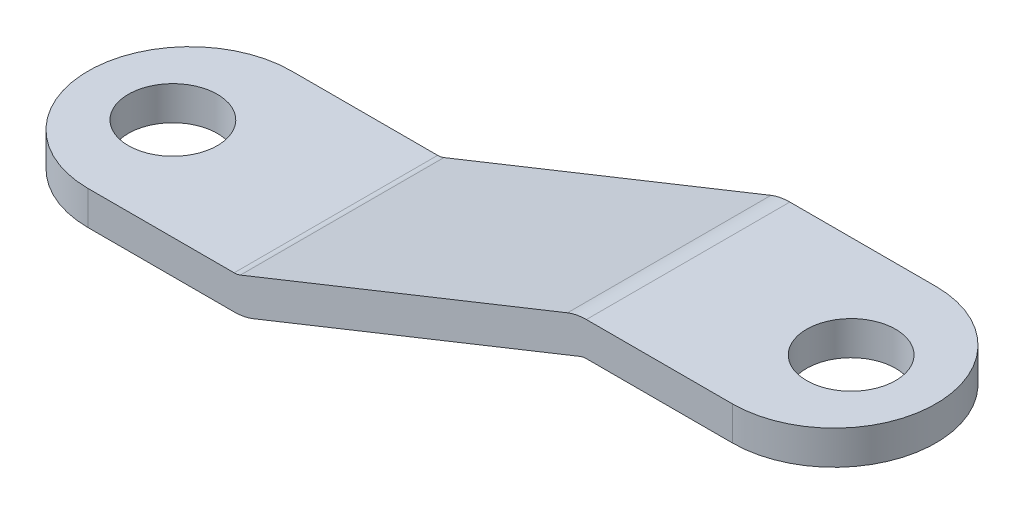
SolidWorks part; units mm, degrees
material "1060 Alloy"
ref_plane "Front Plane" through (0, 0, 0) normal (0, 0, 1) x (1, 0, 0)
ref_plane "Top Plane" through (0, 0, 0) normal (0, 1, 0) x (1, 0, 0)
ref_plane "Right Plane" through (0, 0, 0) normal (1, 0, 0) x (0, 0, -1)
sketch "Sketch1" plane through (0, 0, 0) normal (0, 0, 1) x (1, 0, 0)
  line L0 (0, 0) -> (11.6919, 0)
  line L1 (12.2861, 0.1144) -> (27.7139, 6.2856)
  line L2 (28.3081, 6.4) -> (40, 6.4)
  arc A0 (27.7139, 6.2856) -> (28.3081, 6.4) centre (28.3081, 4.8) cw
  arc A1 (11.6919, 0) -> (12.2861, 0.1144) centre (11.6919, 1.6) ccw
  point P7 (28, 6.4)
  point P10 (12, 0)
  dimension "D5" = 1.6
  dimension "D1" = 12
  dimension "D2" = 12
  dimension "D3" = 6.4
  dimension "D4" = 40
extrude "Extrude-Thin1" add sketch "Sketch1" along normal blind 4.8 thin thin type mid plane wall 1.6
sketch "Sketch2" plane through (0, 0.8, 0) normal (0, 1, 0) x (1, 0, 0)
  line L0 (0, 0) -> (11.6919, 0) construction
  circle A0 centre (4, 0) radius 2.1
  dimension "D1" = 4.2
  dimension "D2" = 4
extrude "Cut-Extrude1" cut sketch "Sketch2" against normal through all
sketch "Sketch3" plane through (0, 7.2, 0) normal (0, 1, 0) x (1, 0, 0)
  line L0 (28.3081, 0) -> (40, 0) construction
  circle A0 centre (36, 0) radius 2.1
  dimension "D2" = 4.2
  dimension "D1" = 4
extrude "Cut-Extrude2" cut sketch "Sketch3" against normal through all
fillet "Fillet1" radius 4.8 2 edges at (0, 0, 4.8) (40, 6.4, 4.8)
mirror "Mirror1" about plane through (28.3081, 4.8, 0) normal (0, 0, 1) of bodies 103 106
